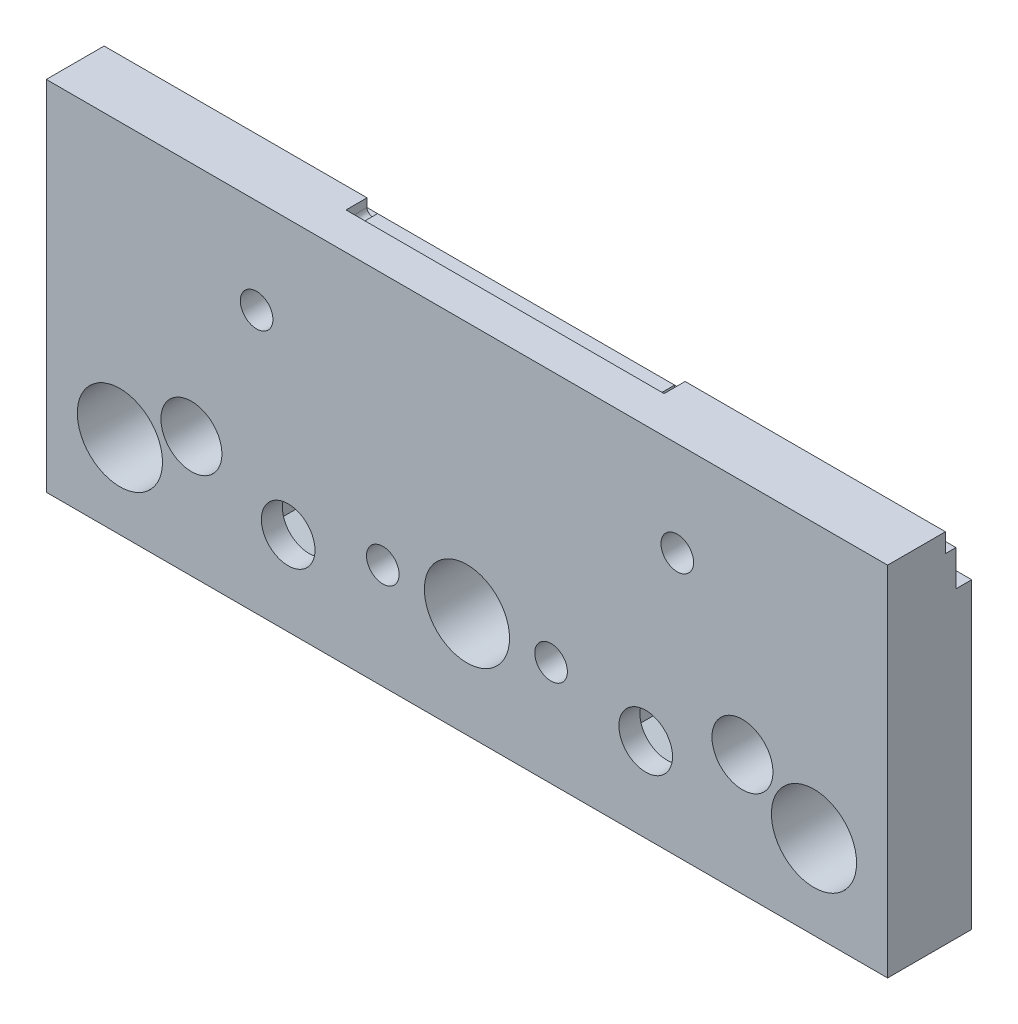
SolidWorks part; units mm, degrees
ref_plane "前视基准面" through (0, 0, 0) normal (0, 0, 1) x (1, 0, 0)
ref_plane "上视基准面" through (0, 0, 0) normal (0, 1, 0) x (1, 0, 0)
ref_plane "右视基准面" through (0, 0, 0) normal (1, 0, 0) x (0, 0, -1)
sketch "前视图草图" plane through (0, 0, 0) normal (0, 0, 1) x (1, 0, 0)
  line L0 (0, 0) -> (44.4821, 0) construction
  line L1 (0, 0) -> (0, 28.3185) construction
sketch "草图2" plane through (0, 0, 0) normal (0, 0, 1) x (1, 0, 0)
  line L0 (0, 0) -> (80, 0)
  line L1 (-200000, 0) -> (200044.4821, 0) construction
  line L2 (80, 0) -> (80, 34)
  line L3 (80, 34) -> (0, 34)
  line L4 (0, -200000) -> (0, 200028.3185) construction
  line L5 (0, 34) -> (0, 0)
  circle A0 centre (7, 8) radius 4.05
  circle A1 centre (40, 10) radius 4.05
  circle A2 centre (73, 8) radius 4.05
  dimension "D3" = 8
  dimension "D5" = 10
  dimension "D9" = 8.1
  dimension "D10" = 8.1
  dimension "D11" = 8.1
  dimension "D1" = 34
  dimension "D2" = 80
  dimension "D4" = 7
  dimension "D6" = 7
  dimension "D7" = 8
  dimension "D8" = 40
extrude "凸台-拉伸1" add sketch "草图2" along normal blind 8
sketch "草图3" plane through (0, 0, 8) normal (0, 0, 1) x (1, 0, 0)
  line L0 (16.088, 8) -> (31.4805, 8) construction
  line L1 (7, 8) -> (7, 16.8386) construction
  line L2 (73, 8) -> (73, 16.5917) construction
  line L4 (-200000, 0) -> (200044.4821, 0) construction
  circle A2 centre (23, 8) radius 2.55
  circle A3 centre (57, 8) radius 2.55
  dimension "D4" = 5.1
  dimension "D5" = 5.1
  dimension "D1" = 8
  dimension "D2" = 16
  dimension "D3" = 16
extrude "切除-拉伸1" cut sketch "草图3" against normal through all
sketch "草图4" plane through (80, 0, 0) normal (1, 0, 0) x (0, 0, -1)
  line L1 (0, -200000) -> (0, 200028.3185) construction
  line L2 (-1.5, 32.2) -> (-2.5, 32.2)
  line L3 (-2.5, 32.2) -> (-2.5, 34)
  line L4 (-8, 34) -> (0, 34) construction
  line L5 (-2.5, 34) -> (0, 34)
  line L6 (-1.5, 32.2) -> (-1.5, 28.8)
  line L7 (-1.5, 28.8) -> (0, 28.8)
  line L8 (0, 28.8) -> (0, 34)
  dimension "D1" = 3.4
  dimension "D2" = 2.5
  dimension "D3" = 1.5
  dimension "D4" = 1.8
extrude "切除-拉伸2" cut sketch "草图4" against normal through all
sketch "草图5" plane through (0, 0, 8) normal (0, 0, 1) x (1, 0, 0)
  line L0 (40, 10) -> (56.5376, 10) construction
  circle A0 centre (40, 10) radius 8 construction
  circle A1 centre (48, 10) radius 1.55
  circle A2 centre (32, 10) radius 1.55
  dimension "D1" = 3.1
  dimension "D2" = 3.1
  dimension "D3" = 16
extrude "切除-拉伸3" cut sketch "草图5" against normal through all
sketch "草图7" plane through (0, 0, 0) normal (0, 0, -1) x (-1, 0, 0)
  line L0 (-40, 12) -> (-40, -8.3696) construction
  line L1 (-23, 10) -> (-23, -2.3368) construction
  line L2 (200000, 0) -> (-200044.4821, 0) construction
  line L6 (-27.05, 10) -> (-27.05, 2.5)
  line L7 (-29.55, 0) -> (-16.45, 0)
  line L8 (-18.95, 2.5) -> (-18.95, 10)
  line L9 (-23, 8) -> (-23, 15.9045) construction
  line L13 (0, -200000) -> (0, 200028.3185) construction
  line L14 (-57, 8) -> (-57, 15.9045) construction
  line L15 (-57, 10) -> (-57, -2.3368) construction
  line L16 (-61.05, 2.5) -> (-61.05, 10)
  line L17 (-50.45, 0) -> (-63.55, 0)
  line L18 (-52.95, 10) -> (-52.95, 2.5)
  arc A1 (-18.95, 10) -> (-27.05, 10) centre (-23, 10) ccw
  arc A4 (-29.55, 0) -> (-27.05, 2.5) centre (-29.55, 2.5) ccw
  arc A5 (-18.95, 2.5) -> (-16.45, 0) centre (-16.45, 2.5) ccw
  arc A7 (-61.05, 2.5) -> (-63.55, 0) centre (-63.55, 2.5) cw
  arc A8 (-50.45, 0) -> (-52.95, 2.5) centre (-50.45, 2.5) cw
  arc A9 (-61.05, 10) -> (-52.95, 10) centre (-57, 10) cw
  dimension "D1" = 40
  dimension "D4" = 8.1
  dimension "D7" = 2.5
  dimension "D8" = 2.5
  dimension "D3" = 10
extrude "切除-拉伸4" [suppressed] cut sketch "草图7" against normal blind 6
sketch "草图8" plane through (0, 0, 0) normal (0, 0, -1) x (-1, 0, 0)
  line L0 (-40, 10) -> (-57.3165, 10) construction
  line L1 (-40, 20) -> (-40, 35.6562) construction
  line L2 (-30.5, 12.85) -> (-49.5, 12.85)
  line L3 (-49.5, 7.15) -> (-30.5, 7.15)
  line L4 (200000, 0) -> (-200044.4821, 0) construction
  line L5 (-80, 0) -> (-80, 28.8) construction
  line L6 (-48, 6.7091) -> (-45.15, 8.3546)
  line L7 (-45.15, 8.3546) -> (-45.15, 11.6454)
  line L8 (-45.15, 11.6454) -> (-48, 13.2909)
  line L9 (-48, 13.2909) -> (-50.85, 11.6454)
  line L10 (-50.85, 11.6454) -> (-50.85, 8.3546)
  line L11 (-50.85, 8.3546) -> (-48, 6.7091)
  line L12 (-34.85, 11.6454) -> (-34.85, 8.3546)
  line L13 (-34.85, 8.3546) -> (-32, 6.7091)
  line L14 (-32, 6.7091) -> (-29.15, 8.3546)
  line L15 (-29.15, 8.3546) -> (-29.15, 11.6454)
  line L16 (-29.15, 11.6454) -> (-32, 13.2909)
  line L17 (-32, 13.2909) -> (-34.85, 11.6454)
  arc A0 (-30.5, 7.15) -> (-30.5, 12.85) centre (-30.5, 10) ccw
  arc A1 (-49.5, 12.85) -> (-49.5, 7.15) centre (-49.5, 10) ccw
  circle A2 centre (-48, 10) radius 2.85 construction
  circle A3 centre (-32, 10) radius 2.85 construction
  dimension "D1" = 5.7
  dimension "D2" = 9.5
  dimension "D3" = 9.5
  dimension "D4" = 10
  dimension "D5" = 5.7
sketch "草图11" plane through (0, 0, 0) normal (0, 0, -1) x (-1, 0, 0)
  line L0 (0, 34) -> (-80, 34) construction
  line L1 (-80, 0) -> (-80, 28.8) construction
  line L2 (0, -200000) -> (0, 200028.3185) construction
  line L3 (-40, 20) -> (-40, 13.5744) construction
  line L4 (-28.772, 25) -> (-45.9396, 25) construction
  circle A0 centre (-60, 25) radius 1.55
  circle A1 centre (-20, 25) radius 1.55
  point P23 (-40, 20)
  dimension "D1" = 3.1
  dimension "D2" = 3.1
  dimension "D3" = 20
  dimension "D4" = 20
  dimension "D5" = 9
sketch "草图20" plane through (0, 0, 0) normal (0, 0, -1) x (-1, 0, 0)
  circle A0 centre (-40, 10) radius 5.5
  dimension "D1" = 11
extrude "切除-拉伸15" cut sketch "草图8" against normal blind 4.5 contours L10 L11 L6 L7 L8 L9 | L13 L14 L15 L16 L17 L12
extrude "切除-拉伸7" cut sketch "草图11" against normal through all contours A0 | A1 region at (60, 25, 0) region at (20, 25, 0)
sketch "草图12" plane through (0, 0, 0) normal (0, 0, -1) x (-1, 0, 0)
  line L0 (-62.5, 22.15) -> (-57.5, 22.15)
  line L1 (-57.5, 27.85) -> (-62.5, 27.85)
  line L4 (-80, 0) -> (-80, 28.8) construction
  line L5 (-39.1423, 25) -> (-43.2672, 25) construction
  line L6 (-60, 21) -> (-60, 25.2385) construction
  line L7 (-20, 21) -> (-20, 26.1603) construction
  line L8 (-40, 20) -> (-40, 24.3689) construction
  line L9 (-17.5, 27.85) -> (-22.5, 27.85)
  line L10 (-22.5, 22.15) -> (-17.5, 22.15)
  line L11 (0, -200000) -> (0, 200028.3185) construction
  line L12 (0, 34) -> (-80, 34) construction
  arc A0 (-62.5, 27.85) -> (-62.5, 22.15) centre (-62.5, 25) ccw
  arc A1 (-57.5, 22.15) -> (-57.5, 27.85) centre (-57.5, 25) ccw
  arc A4 (-17.5, 22.15) -> (-17.5, 27.85) centre (-17.5, 25) ccw
  arc A5 (-22.5, 27.85) -> (-22.5, 22.15) centre (-22.5, 25) ccw
  point P16 (-38, 21)
  point P28 (-40, 25)
  dimension "D2" = 20
  dimension "D3" = 5
  dimension "D4" = 2.5
  dimension "D5" = 20
  dimension "D6" = 9
  dimension "D1" = 2
sketch "草图19" plane through (0, 0, 2.5) normal (0, 0, -1) x (-1, 0, 0)
  line L0 (0, 34) -> (-80, 34) construction
  line L1 (-25, 34) -> (-55.2479, 34)
  line L2 (-25, 34) -> (-25, 33.2)
  line L3 (-26, 33.2) -> (-54.2479, 33.2)
  line L4 (-55.2479, 34) -> (-55.2479, 33.2)
  line L5 (0, -200000) -> (0, 200028.3185) construction
  line L7 (0, 32.2) -> (-80, 32.2) construction
  line L8 (-56.3335, 32.7) -> (-52.9089, 32.7) construction
  line L9 (-55.2479, 1028.5823) -> (-55.2479, 33.2) construction
  line L10 (-25, 1028.5823) -> (-25, 32.7) construction
  line L11 (-55.2479, 32.7) -> (-55.2479, -973.3) construction
  line L12 (-25, 32.7) -> (-25, -973.3) construction
  arc A3 (-55.2479, 33.2) -> (-54.2479, 33.2) centre (-54.7479, 33.2) ccw
  arc A6 (-26, 33.2) -> (-25, 33.2) centre (-25.5, 33.2) ccw
  dimension "D3" = 1
  dimension "D4" = 1
  dimension "D2" = 0.8
  dimension "D1" = 0.5
  dimension "D9" = 25
extrude "切除-拉伸11" cut sketch "草图19" against normal blind 2
sketch "草图21" plane through (0, 0, 0) normal (0, 0, -1) x (-1, 0, 0)
  line L0 (-80, 11.5) -> (0, 11.5) construction
  line L1 (-80, 0) -> (-80, 28.8) construction
  line L2 (0, -200000) -> (0, 200028.3185) construction
  line L3 (-66.2, 28.8) -> (-66.2, 0) construction
  line L4 (0, 28.8) -> (-80, 28.8) construction
  line L5 (200000, 0) -> (-200044.4821, 0) construction
  line L6 (-40, 28.8) -> (-40, 0) construction
  line L7 (-40, -199980) -> (-40, 200024.3689) construction
  circle A0 centre (-66.2, 11.5) radius 2.9
  circle A1 centre (-13.8, 11.5) radius 2.9
  dimension "D3" = 5.8
  dimension "D1" = 11.5
  dimension "D2" = 13.8
extrude "切除-拉伸13" cut sketch "草图21" against normal through all
sketch "草图22" plane through (0, 0, 0) normal (0, 0, -1) x (-1, 0, 0)
  line L0 (-80, 0) -> (-80, 28.8) construction
  line L1 (-52.9, 5.6329) -> (-52.9, 10.3671)
  line L2 (-52.9, 10.3671) -> (-57, 12.7343)
  line L3 (-57, 12.7343) -> (-61.1, 10.3671)
  line L4 (-61.1, 10.3671) -> (-61.1, 5.6329)
  line L5 (-61.1, 5.6329) -> (-57, 3.2657)
  line L6 (-57, 3.2657) -> (-52.9, 5.6329)
  line L7 (-23, 3.2657) -> (-18.9, 5.6329)
  line L8 (-18.9, 5.6329) -> (-18.9, 10.3671)
  line L9 (-18.9, 10.3671) -> (-23, 12.7343)
  line L10 (-23, 12.7343) -> (-27.1, 10.3671)
  line L11 (-27.1, 10.3671) -> (-27.1, 5.6329)
  line L12 (-27.1, 5.6329) -> (-23, 3.2657)
  circle A0 centre (-57, 8) radius 4.1 construction
  circle A1 centre (-23, 8) radius 4.1 construction
  dimension "D1" = 8.2
extrude "切除-拉伸14" cut sketch "草图22" against normal blind 6
